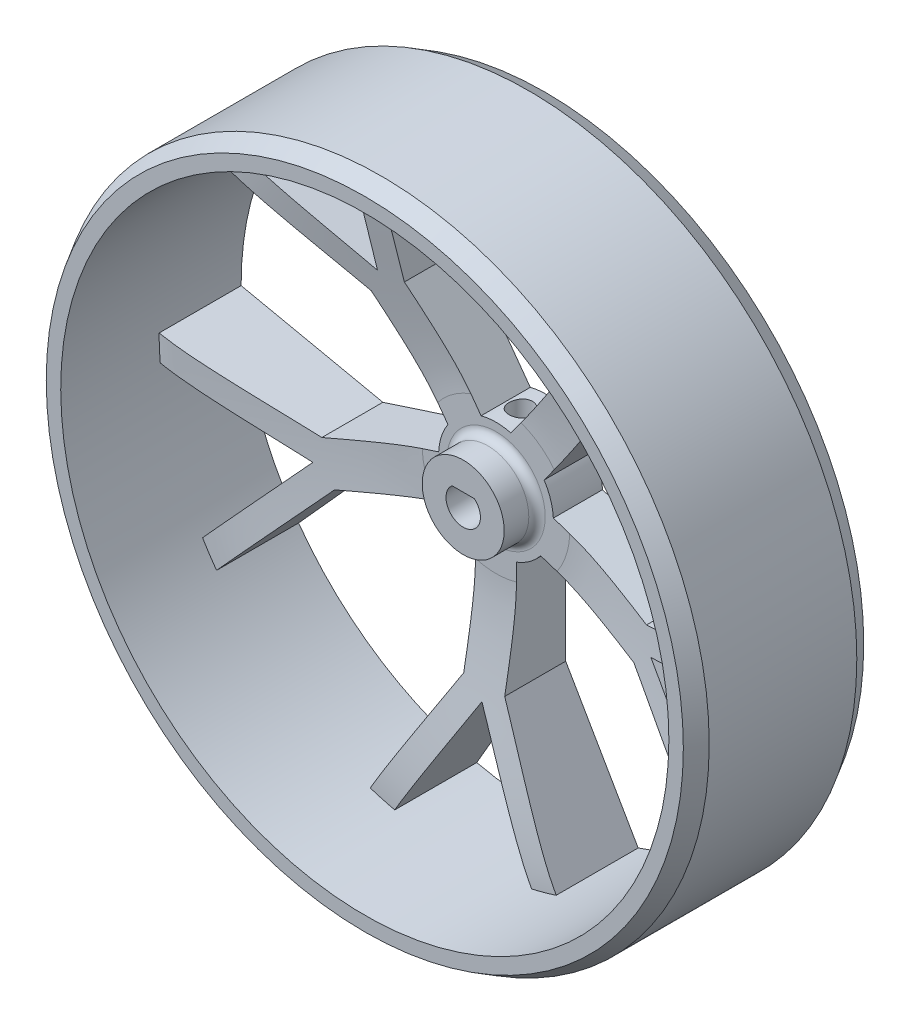
SolidWorks part; units mm, degrees
note: The reader was unsure of these and kept them because the rebuilt part matched: shared geometry of "Sketch1<6>", "Sketch1<7>".
material "ABS"
ref_plane "Front Plane" through (0, 0, 0) normal (0, 0, 1) x (1, 0, 0)
ref_plane "Top Plane" through (0, 0, 0) normal (0, 1, 0) x (1, 0, 0)
ref_plane "Right Plane" through (0, 0, 0) normal (1, 0, 0) x (0, 0, -1)
sketch "Sketch1" plane through (0, 0, 0) normal (0, 0, 1) x (1, 0, 0)
  line L0 (0, -2.1) -> (0, 1.6) construction
  line L1 (-1.3601, 1.6) -> (1.3601, 1.6)
  line L2 (0, -20) -> (2.5, -20) construction
  line L3 (2.5, -6.5383) -> (2.5, -20)
  line L4 (2.5, -20) -> (11.3367, -35.3056)
  line L5 (6.9183, -27.6528) -> (4.3203, -29.1528) construction
  line L6 (4.3203, -29.1528) -> (8.348, -36.1291) construction
  line L7 (8.348, -36.1291) -> (0, -21.6699)
  line L8 (-8.348, -36.1291) -> (0, -21.6699)
  line L9 (-2.5, -20) -> (-11.3367, -35.3056)
  line L10 (-2.5, -6.5383) -> (-2.5, -20)
  line L11 (-18.2486, -8.558) -> (-30.0744, -21.6918)
  line L12 (-31.7811, -19.104) -> (-20.6093, -6.6964)
  line L13 (-36.9405, -3.225) -> (-20.6093, -6.6964)
  line L14 (-19.7937, -3.8027) -> (-37.0808, -0.1282)
  line L15 (-6.9909, 0.3572) -> (-19.7937, -3.8027)
  line L16 (-5.4458, -4.3981) -> (-18.2486, -8.558)
  line L17 (-13.7782, 14.7109) -> (-29.9236, 21.8993)
  line L18 (-27.9899, 24.3222) -> (-12.7372, 17.5313)
  line L19 (-14.4824, 34.1359) -> (-12.7372, 17.5313)
  line L20 (-9.7332, 17.6498) -> (-11.5805, 35.2263)
  line L21 (-1.8206, 6.7591) -> (-9.7332, 17.6498)
  line L22 (-5.8657, 3.8202) -> (-13.7782, 14.7109)
  line L23 (9.7332, 17.6498) -> (11.5805, 35.2263)
  line L24 (14.4824, 34.1359) -> (12.7372, 17.5313)
  line L25 (27.9899, 24.3222) -> (12.7372, 17.5313)
  line L26 (13.7782, 14.7109) -> (29.9236, 21.8993)
  line L27 (5.8657, 3.8202) -> (13.7782, 14.7109)
  line L28 (1.8206, 6.7591) -> (9.7332, 17.6498)
  line L29 (19.7937, -3.8027) -> (37.0808, -0.1282)
  line L30 (36.9405, -3.225) -> (20.6093, -6.6964)
  line L31 (31.7811, -19.104) -> (20.6093, -6.6964)
  line L32 (18.2486, -8.558) -> (30.0744, -21.6918)
  line L33 (5.4458, -4.3981) -> (18.2486, -8.558)
  line L34 (6.9909, 0.3572) -> (19.7937, -3.8027)
  line L44 (0, 0) -> (0, -40) construction
  circle A0 centre (0, 0) radius 40
  arc A1 (-1.3601, 1.6) -> (1.3601, 1.6) centre (0, 0) ccw
  circle A2 centre (0, 0) radius 7
  circle A7 centre (0, 0) radius 37.081
  point P59 (0, 0)
  point P67 (0, 0)
  dimension "D1" = 5
extrude "Boss-Extrude1" add sketch "Sketch1" along normal blind 10
extrude "Boss-Extrude3" add sketch "Sketch1<6>" along normal blind 22 contours A0 A7
sketch "Sketch1<6>" plane through (0, 0, 0) normal (0, 0, 1) x (1, 0, 0) same geometry as "Sketch1"
extrude "Boss-Extrude4" add sketch "Sketch1<7>" along normal blind 10 contours A2 A1 L1
sketch "Sketch1<7>" plane through (0, 0, 0) normal (0, 0, 1) x (1, 0, 0) same geometry as "Sketch1"
sketch "Sketch3" plane through (0, 0, 0) normal (0, 1, 0) x (1, 0, 0)
  line L0 (0, -10) -> (5, -10) construction
  line L1 (-2.1, -10) -> (2.1, -10) construction
  line L2 (0, -10) -> (0, 0) construction
  line L3 (5, -10) -> (13, -10)
  line L4 (5, -10) -> (5, -7)
  line L5 (6, -6) -> (9, -6)
  line L6 (13, -10) -> (37.0808, -10)
  line L7 (19.7937, -10) -> (37.0808, -10) construction
  line L8 (37.0808, -10) -> (37.0808, 0) construction
  arc A1 (6, -6) -> (5, -7) centre (6, -7) ccw
  spline S0 degree 3 poles (9, -6) (15.881, -6) (30.466, -9.9791) (37.0808, -10) knots 0 0 0 0 1 1 1 1
revolve "Cut-Revolve1" cut sketch "Sketch3" angle 360 about L2
chamfer "Chamfer1" distance 2 angle 30 1 edges at (40, 0, 22)
chamfer "Chamfer2" distance 2 angle 30 1 edges at (40, 0, 0)
sketch "Sketch4" plane through (0, 1.6, 0) normal (0, -1, 0) x (1, 0, 0)
  line L1 (0, 0) -> (0, 3) construction
  line L2 (-1.3601, 0) -> (1.3601, 0) construction
  circle A0 centre (0, 3) radius 1.42
extrude "Cut-Extrude1" cut sketch "Sketch4" against normal blind 10 contours A0
